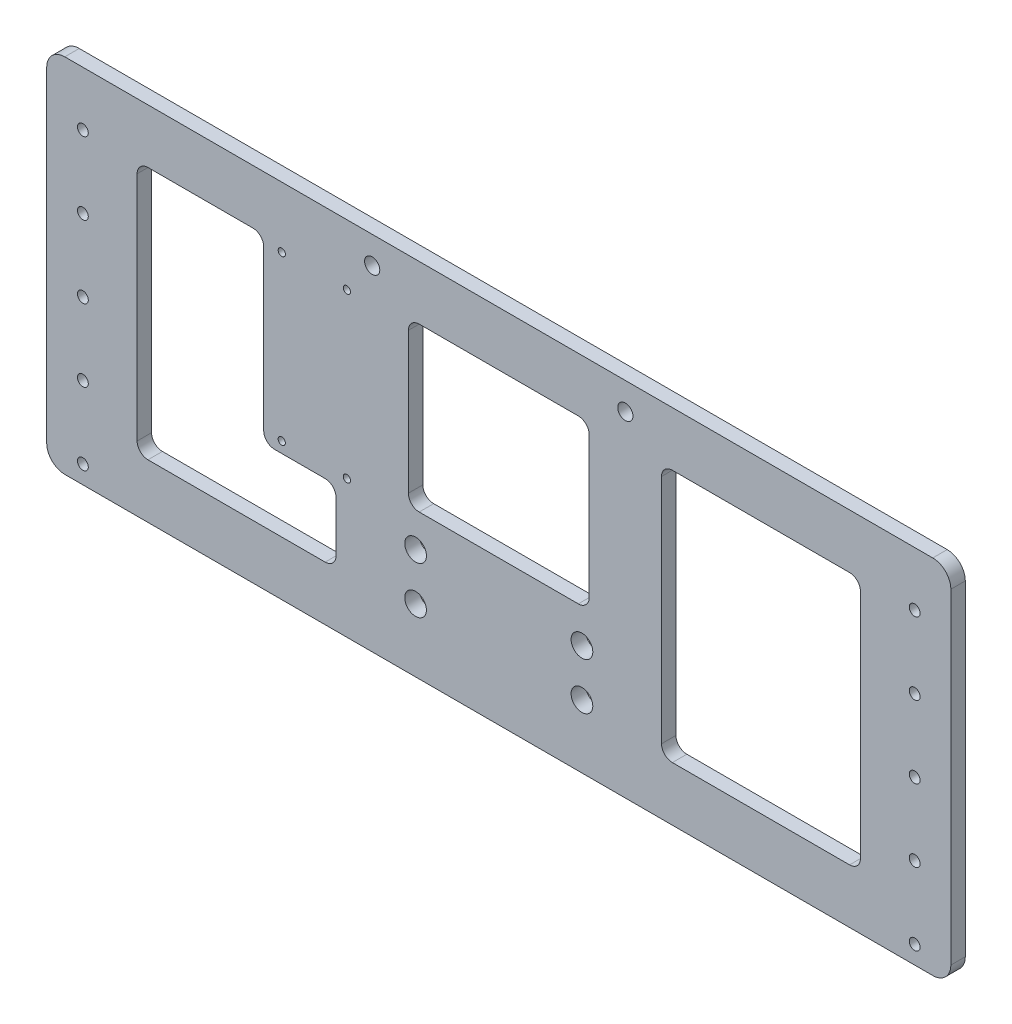
SolidWorks part; units mm, degrees
material "默认 (3)"
ref_plane "前视基准面" through (0, 0, 0) normal (0, 0, 1) x (1, 0, 0)
ref_plane "上视基准面" through (0, 0, 0) normal (0, 1, 0) x (1, 0, 0)
ref_plane "右视基准面" through (0, 0, 0) normal (1, 0, 0) x (0, 0, -1)
other "Configuration Table"
sketch "草图1" plane through (0, 0, 0) normal (0, 0, 1) x (1, 0, 0)
  line L0 (0, 0) -> (0, -50000) construction
  line L1 (-125, 15) -> (125, 15)
  line L2 (-125, 15) -> (-125, -15)
  line L3 (-125, -15) -> (125, -15)
  line L4 (125, 15) -> (125, -15)
  line L5 (-125, 15) -> (125, -15) construction
  line L6 (-125, -15) -> (125, 15) construction
  line L7 (-115, -10) -> (-115, 10) construction
  circle A0 centre (-115, -10) radius 1.5
  circle A1 centre (-115, 10) radius 1.5
  circle A2 centre (115, 10) radius 1.5
  circle A3 centre (115, -10) radius 1.5
  point P0 (0, 0)
  dimension "D6" = 5
  dimension "D7" = 3
  dimension "D1" = 250
  dimension "D2" = 30
  dimension "D4" = 20
  dimension "D5" = 10
  dimension "D3" = 2
extrude "凸台-拉伸1" add sketch "草图1" along normal blind 4
sketch "草图2" plane through (0, 0, 4) normal (0, 0, 1) x (1, 0, 0)
  line L0 (0, 0) -> (0, -50000) construction
  line L1 (0, 9) -> (50000, 9) construction
  line L2 (-23, 2.5) -> (23, 2.5) construction
  line L3 (-23, 2.5) -> (-23, 15.5) construction
  line L4 (-125, -15) -> (125, -15) construction
  circle A0 centre (-23, 2.5) radius 3
  circle A1 centre (23, 2.5) radius 3
  circle A2 centre (23, 15.5) radius 3
  circle A3 centre (-23, 15.5) radius 3
  dimension "D5" = 6
  dimension "D3" = 46
  dimension "D4" = 13
  dimension "D6" = 24
  dimension "D1" = 2
  dimension "D2" = 2
extrude "切除-拉伸1" cut sketch "草图2" against normal through all
sketch "草图3" plane through (0, 0, 4) normal (0, 0, 1) x (1, 0, 0)
  line L0 (0, 54.5) -> (0, -49945.5) construction
  line L1 (-125, 85) -> (125, 85)
  line L2 (-125, 85) -> (-125, 15)
  line L3 (-125, 15) -> (125, 15)
  line L4 (125, 85) -> (125, 15)
  line L5 (-125, 85) -> (125, 15) construction
  line L6 (-125, 15) -> (125, 85) construction
  line L8 (-115, 10) -> (-115, 30) construction
  circle A4 centre (-115, 10) radius 1.5 construction
  circle A5 centre (-115, 10) radius 1.5
  circle A6 centre (-115, 30) radius 1.5
  circle A7 centre (-115, 50) radius 1.5
  circle A8 centre (-115, 70) radius 1.5
  circle A9 centre (-115, 90) radius 1.5
  circle A10 centre (115, 10) radius 1.5
  circle A11 centre (115, 30) radius 1.5
  circle A12 centre (115, 50) radius 1.5
  circle A13 centre (115, 70) radius 1.5
  circle A14 centre (-35, 77.5) radius 2.1
  circle A15 centre (35, 77.5) radius 2.1
  point P0 (0, 50)
  line M16 (125, 15) -> (25.958, 15)
  dimension "D4" = 70
  dimension "D2" = 4.2
  dimension "D3" = 7.5
  dimension "D1" = 70
  dimension "D7" = 20
  dimension "D6" = 5
extrude "凸台-拉伸2" add sketch "草图3" against normal blind 4 contours L4 L1 L2 A12 A14 A6 A7 A8 A11 A13 M16 region at (0, 49.9563, 4)
sketch "草图4" plane through (0, 0, 4) normal (0, 0, 1) x (1, 0, 0)
  line L0 (0, 0) -> (0, -50000) construction
  line L1 (-125, 85) -> (125, 85) construction
  line L2 (-22, 70) -> (22, 70)
  line L3 (-25, 67) -> (-25, 28)
  line L4 (-22, 25) -> (22, 25)
  line L5 (25, 67) -> (25, 28)
  line L6 (-25, 70) -> (25, 25) construction
  line L7 (-25, 25) -> (25, 70) construction
  line L8 (-125, -15) -> (125, -15) construction
  line L9 (-97, 70) -> (-48, 70)
  line L10 (-100, 67) -> (-100, 3)
  line L11 (-97, 0) -> (-48, 0)
  line L12 (-45, 67) -> (-45, 3)
  line L13 (-100, 70) -> (-45, 0) construction
  line L14 (-100, 0) -> (-45, 70) construction
  line L15 (-125, 85) -> (-125, -15) construction
  line L16 (97, 0) -> (48, 0)
  line L17 (45, 67) -> (45, 3)
  line L18 (97, 70) -> (48, 70)
  line L19 (100, 67) -> (100, 3)
  arc A0 (22, 70) -> (25, 67) centre (22, 67) cw
  arc A1 (22, 25) -> (25, 28) centre (22, 28) ccw
  arc A2 (-25, 28) -> (-22, 25) centre (-22, 28) ccw
  arc A3 (-22, 70) -> (-25, 67) centre (-22, 67) ccw
  arc A4 (-48, 0) -> (-45, 3) centre (-48, 3) ccw
  arc A5 (-100, 3) -> (-97, 0) centre (-97, 3) ccw
  arc A6 (-48, 70) -> (-45, 67) centre (-48, 67) cw
  arc A7 (-97, 70) -> (-100, 67) centre (-97, 67) ccw
  arc A8 (48, 0) -> (45, 3) centre (48, 3) cw
  arc A9 (48, 70) -> (45, 67) centre (48, 67) ccw
  arc A10 (100, 3) -> (97, 0) centre (97, 3) cw
  arc A11 (97, 70) -> (100, 67) centre (97, 67) cw
  point P3 (0, 47.5)
  point P10 (-72.5, 35)
  dimension "D8" = 3
  dimension "D1" = 15
  dimension "D2" = 45
  dimension "D3" = 50
  dimension "D4" = 15
  dimension "D5" = 15
  dimension "D6" = 25
  dimension "D7" = 55
extrude "切除-拉伸2" cut sketch "草图4" against normal through all
fillet "圆角1" radius 5 4 edges at (125, -15, 2) (125, 85, 2) (-125, -15, 2) (-125, 85, 2)
sketch "草图5" plane through (0, 0, 4) normal (0, 0, 1) x (1, 0, 0)
  circle A0 centre (-23, 15.5) radius 3
  circle A1 centre (23, 15.5) radius 3
  dimension "D1" = 6
extrude "切除-拉伸3" cut sketch "草图5" against normal through all
sketch "草图8" plane through (0, 0, 4) normal (0, 0, 1) x (1, 0, 0)
  line L0 (-48, 70) -> (-97, 70) construction
  line L1 (-45, 70) -> (-65, 70)
  line L2 (-45, 70) -> (-45, 20)
  line L3 (-45, 20) -> (-65, 20)
  line L4 (-65, 70) -> (-65, 20)
  line L5 (-45, 3) -> (-45, 67) construction
  dimension "D1" = 50
  dimension "D2" = 20
extrude "凸台-拉伸4" add sketch "草图8" against normal up to surface (4 mm away) up to face at (72.5, 35, 0)
sketch "草图9" plane through (0, 0, 4) normal (0, 0, 1) x (1, 0, 0)
  line L0 (-65, 20) -> (-45, 20) construction
  line L1 (-65, 70) -> (-65, 20) construction
  circle A0 centre (-60, 23) radius 1
  circle A1 centre (-42, 23) radius 1
  circle A2 centre (-60, 68.2) radius 1
  circle A3 centre (-42, 68.2) radius 1
  dimension "D1" = 2
  dimension "D4" = 3
  dimension "D5" = 5
  dimension "D2" = 2
  dimension "D3" = 2
extrude "切除-拉伸4" cut sketch "草图9" against normal blind 10
fillet "圆角3" radius 3 3 edges at (-45, 20, 2) (-65, 70, 2) (-65, 20, 2)
